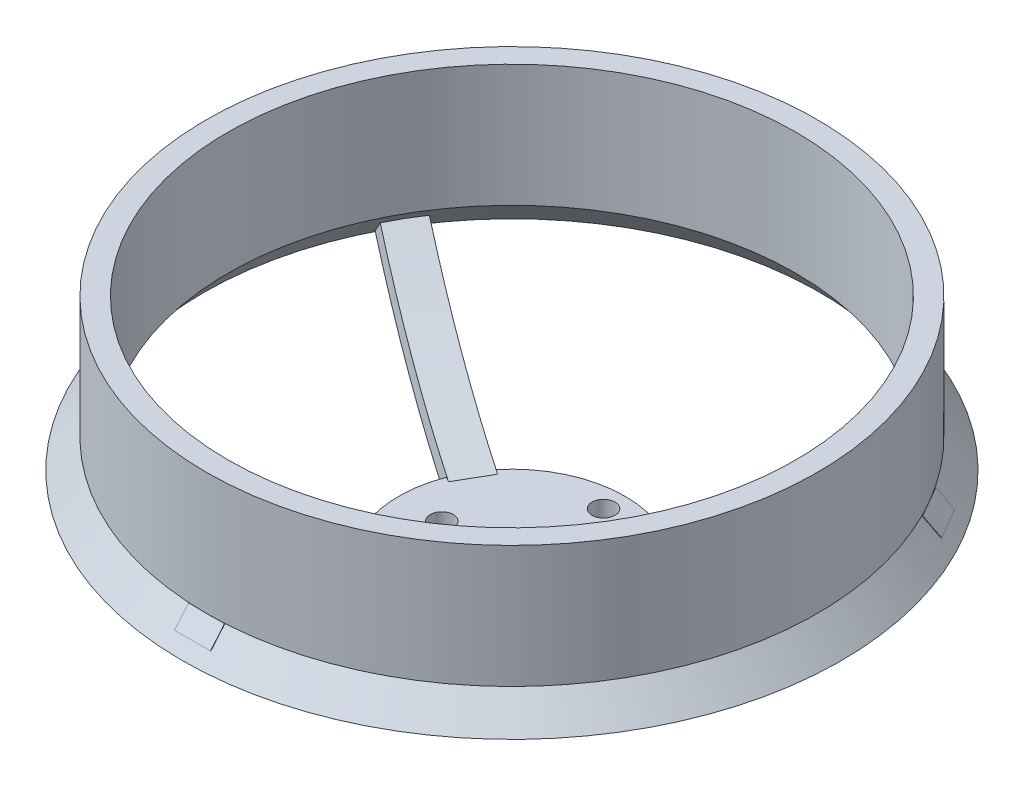
SolidWorks part; units mm, degrees
ref_plane "前视基准面" through (0, 0, 0) normal (0, 0, 1) x (1, 0, 0)
ref_plane "上视基准面" through (0, 0, 0) normal (0, 1, 0) x (1, 0, 0)
ref_plane "右视基准面" through (0, 0, 0) normal (1, 0, 0) x (0, 0, -1)
sketch "草图1" plane through (0, 0, 0) normal (0, 1, 0) x (1, 0, 0)
  line L0 (0, 0) -> (10.4428, 0) construction
  line L1 (0, 0) -> (0, 7.4071) construction
  circle A2 centre (0, 0) radius 15.75
  circle A3 centre (0, 12.75) radius 1.6
  circle A4 centre (0, -12.75) radius 1.6
  circle A5 centre (-9.75, 0) radius 1.6
  circle A6 centre (9.75, 0) radius 1.6
  circle A7 centre (0, 0) radius 3
  dimension "D1" = 3.2
  dimension "D2" = 31.5
  dimension "D5" = 6
  dimension "D3" = 19.5
  dimension "D4" = 25.5
extrude "凸台-拉伸1" add sketch "草图1" along normal blind 4
ref_plane "基准面4" through (0, 19, 0) normal (0, 1, 0) x (1, 0, 0)
sketch "草图2" plane through (0, 19, 0) normal (0, 1, 0) x (1, 0, 0)
  circle A0 centre (0, 0) radius 42.5
  circle A1 centre (0, 0) radius 39.5
  dimension "D1" = 79
  dimension "D2" = 85
extrude "凸台-拉伸2" add sketch "草图2" along normal blind 17 separate body
sketch "草图3" plane through (0, 0, 0) normal (1, 0, 0) x (0, 0, -1)
  line L4 (-42.5, 24.3065) -> (-42.5, 10.9071) construction
  line L5 (-14.75, 6.1412) -> (-14.75, -1.8173) construction
  line L12 (-15.75, 4) -> (-15.75, 0) construction
  line L13 (15.75, 4) -> (-15.75, 4) construction
  line L14 (-52.8, 20.191) -> (-52.8, 20.2145)
  line L19 (-39.5, 19) -> (-42.5, 19)
  line L21 (-14.75, 4) -> (-14.75, 1)
  arc A2 (-14.75, 4) -> (-39.5, 19) centre (5.5247, 65.372) cw
  arc A4 (-14.75, 1) -> (-42.5, 19) centre (0.3533, 54.6749) cw
  dimension "D1" = 1
  dimension "D2" = 3
ref_axis "基准轴1" through (0, 0, 0) along (0, 1, 0)
sketch "草图5" plane through (0, 0, 0) normal (0, 0, 1) x (1, 0, 0)
  line L0 (0, 19) -> (0, 15)
  line L1 (-42.5, 36) -> (-42.5, 19) construction
  line L2 (-42.5, 19) -> (-45.8564, 15)
  line L6 (-45.8564, 15) -> (-42.8564, 15)
  line L7 (17.325, 19) -> (-17.325, 19) construction
  line L9 (-52.8, 19) -> (0, 19)
  line L10 (-42.8564, 15) -> (-39.5, 19)
  line L11 (-42.5, 19) -> (-39.5, 19)
  dimension "D2" = 140
  dimension "D3" = 3
revolve "旋转3" add sketch "草图5" angle 360 about L0 region at (-42.6782, 17, 0)
sketch "草图6" plane through (0, 0, 0) normal (1, 0, 0) x (0, 0, -1)
  line L0 (-14.75, 4) -> (-14.75, 1)
  line L1 (-42.5, 19) -> (-45.8564, 15) construction
  line L2 (15.75, 4) -> (-15.75, 4) construction
  line L3 (-42.5, 19) -> (-44.4284, 16.7019)
  line L5 (-15.75, 4) -> (-15.75, 0) construction
  arc A2 (-42.5, 19) -> (-14.75, 4) centre (3.4099, 70.7645) ccw
  arc A3 (-44.4284, 16.7019) -> (-14.75, 1) centre (2.3962, 69.3071) ccw
  dimension "D1" = 1
  dimension "D2" = 3
  dimension "D3" = 3
extrude "凸台-拉伸6" add sketch "草图6" along normal mid plane 5
pattern_circular "阵列(圆周)4" count 3 over 360 about axis through (0, 4, 0) along (0, -1, 0) of "凸台-拉伸6"
